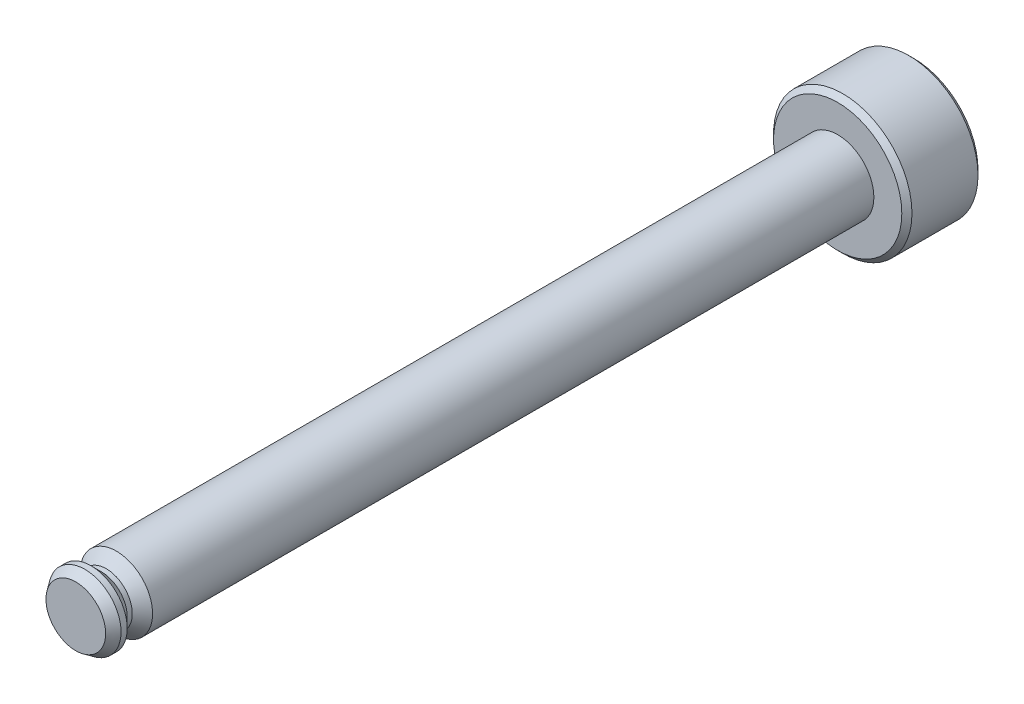
SolidWorks part; units mm, degrees
ref_plane "Front" through (0, 0, 0) normal (0, 0, 1) x (1, 0, 0)
ref_plane "Top" through (0, 0, 0) normal (0, 1, 0) x (1, 0, 0)
ref_plane "Right" through (0, 0, 0) normal (1, 0, 0) x (0, 0, -1)
sketch "Sketch2" plane through (0, 0, 0) normal (0, 0, 1) x (1, 0, 0)
  circle A0 centre (0, 0) radius 1.425
  dimension "D1" = 2.85
extrude "Shaft" add sketch "Sketch2" along normal blind 30
sketch "Sketch5" plane through (0, 0, 0) normal (0, 0, 1) x (1, 0, 0)
  circle A0 centre (0, 0) radius 2.725
  dimension "D1" = 5.45
extrude "Head" add sketch "Sketch5" against normal blind 3
sketch "Sketch4" plane through (0, 0, 0) normal (1, 0, 0) x (0, 0, -1)
  line L0 (0, 0) -> (-18.9, 0) construction
  line L1 (-18.9, 0) -> (-18.9, 4.3666) construction
  line L2 (-19.4, 1.425) -> (-18.4, 1.425)
  line L3 (0, 1.425) -> (-30, 1.425) construction
  line L6 (-18.4, 1.425) -> (-18.8, 1.025)
  line L7 (-18.8, 1.025) -> (-19, 1.025)
  line L8 (-19, 1.025) -> (-19.4, 1.425)
  line L10 (-18.9, 50) -> (-18.9, -50) construction
  dimension "D2" = 1
  dimension "D3" = 45
  dimension "D4" = 0.4
revolve "e-Clip Notch Short" [suppressed] cut sketch "Sketch4" angle 360 about L0
chamfer "Chamfer1" distance 0.25 angle 55 1 edges at (1.425, 0, 30) first distance on face at (1.425, 0, 30)
chamfer "Deburs" distance 0.2 angle 45 2 edges at (2.725, 0, 0) (2.725, 0, -3)
sketch "Sketch6" plane through (0, 0, 0) normal (1, 0, 0) x (0, 0, -1)
  line L0 (0, 0) -> (-28.9, 0) construction
  line L1 (-28.9, 0) -> (-28.9, 1.025) construction
  line L2 (0, 1.425) -> (-29.643, 1.425) construction
  line L3 (-29.4, 1.425) -> (-28.4, 1.425)
  line L4 (-28.4, 1.425) -> (-28.8, 1.025)
  line L5 (-28.8, 1.025) -> (-29, 1.025)
  line L6 (-29, 1.025) -> (-29.4, 1.425)
  line L7 (-28.9, 1.025) -> (-28.9, 1.425) construction
  line L8 (-19.4, 1.425) -> (-18.4, 1.425) construction
  line L9 (-19, 1.025) -> (-19.4, 1.425) construction
  line L10 (-28.9, 50) -> (-28.9, -50) construction
revolve "e-Clip Notch Long" cut sketch "Sketch6" angle 360 about L0
equation "\"D1@Sketch2\"=\"Plastic Hardware OD@Box Assy.Assembly\""
equation "\"D1@Sketch5\"=\"Hardware Head Countersink Diameter@Box Assy.Assembly\"-.3mm"
equation "\"D1@Head\"=\"Countersink Depth@Box Assy.Assembly\""
